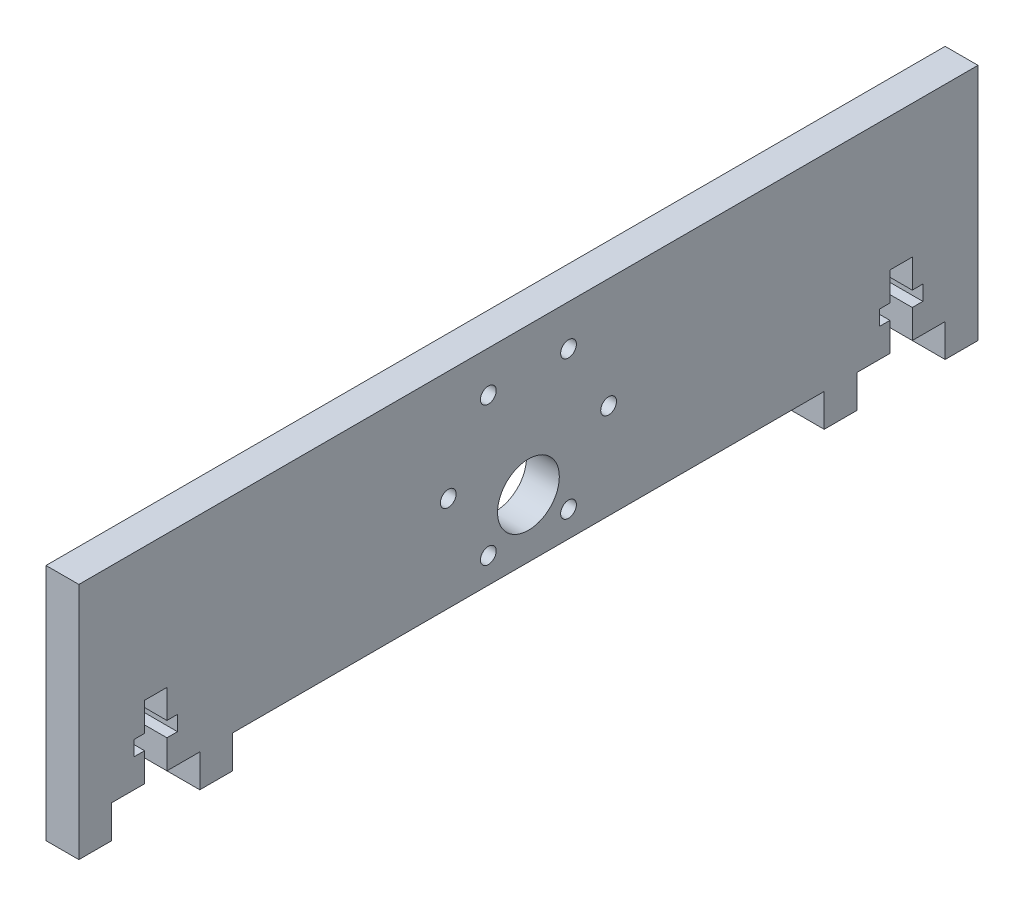
SolidWorks part; units mm, degrees
ref_plane "Front Plane" through (0, 0, 0) normal (0, 0, 1) x (1, 0, 0)
ref_plane "Top Plane" through (0, 0, 0) normal (0, 1, 0) x (1, 0, 0)
ref_plane "Right Plane" through (0, 0, 0) normal (1, 0, 0) x (0, 0, -1)
sketch "Motor plate" plane through (0, 0, 0) normal (1, 0, 0) x (0, 0, -1)
  line L0 (0, -1.4386) -> (7.747, 11.9796) construction
  line L1 (57.15, -19.8536) -> (-57.15, -19.8536)
  line L2 (57.15, -19.8536) -> (57.15, 19.8536) construction
  line L3 (57.15, 19.8536) -> (-57.15, 19.8536)
  line L4 (-57.15, -19.8536) -> (-57.15, 19.8536) construction
  line L5 (57.15, -19.8536) -> (-57.15, 19.8536) construction
  line L6 (57.15, 19.8536) -> (-57.15, -19.8536) construction
  line L7 (86.868, 19.8536) -> (57.15, 19.8536)
  line L8 (86.868, -19.8536) -> (86.868, 19.8536)
  line L9 (-86.868, -26.2036) -> (86.868, -26.2036) construction
  line L13 (0, 19.8536) -> (0, -19.8536) construction
  line L21 (-86.868, -19.8536) -> (-86.868, 19.8536)
  line L22 (-86.868, 19.8536) -> (-57.15, 19.8536)
  circle A0 centre (7.747, 11.9796) radius 1.524
  circle A1 centre (15.494, -1.4386) radius 1.524
  circle A2 centre (7.747, -14.8568) radius 1.524
  circle A3 centre (-7.747, -14.8568) radius 1.524
  circle A4 centre (-15.494, -1.4386) radius 1.524
  circle A5 centre (-7.747, 11.9796) radius 1.524
  circle A6 centre (0, -8.5506) radius 5.969
  circle A7 centre (0, -1.4386) radius 18.415 construction
  point P0 (0, 0)
  point P15 (0, -1.4386)
  point P32 (0, -1.4386)
  line B0 (-80.518, -19.8536) -> (-80.518, -26.2036)
  line B1 (-80.518, -26.2036) -> (-86.868, -26.2036)
  line B2 (-86.868, -26.2036) -> (-86.868, -19.8536)
  line B3 (-74.168, -19.8536) -> (-74.168, -14.3186)
  line B4 (-74.168, -14.3186) -> (-76.209, -14.3186)
  line B5 (-76.209, -14.3186) -> (-76.209, -11.4186)
  line B6 (-76.209, -11.4186) -> (-74.168, -11.4186)
  line B7 (-74.168, -11.4186) -> (-74.168, -5.8836)
  line B8 (-74.168, -5.8836) -> (-69.85, -5.8836)
  line B9 (-69.85, -5.8836) -> (-69.85, -11.4186)
  line B10 (-69.85, -11.4186) -> (-67.809, -11.4186)
  line B11 (-67.809, -11.4186) -> (-67.809, -14.3186)
  line B12 (-67.809, -14.3186) -> (-69.85, -14.3186)
  line B13 (-69.85, -14.3186) -> (-69.85, -19.8536)
  line B14 (-72.009, -5.8836) -> (-72.009, -19.8536) construction
  line B15 (-63.5, -19.8536) -> (-69.85, -19.8536)
  line B16 (-57.15, -26.2036) -> (-57.15, -19.8536)
  line B17 (-80.518, -19.8536) -> (-74.168, -19.8536)
  line B18 (-63.5, -26.2036) -> (-57.15, -26.2036)
  line B19 (-63.5, -19.8536) -> (-63.5, -26.2036)
  line B20 (80.518, -19.8536) -> (80.518, -26.2036)
  line B21 (80.518, -26.2036) -> (86.868, -26.2036)
  line B22 (86.868, -26.2036) -> (86.868, -19.8536)
  line B23 (74.168, -19.8536) -> (74.168, -14.3186)
  line B24 (74.168, -14.3186) -> (76.209, -14.3186)
  line B25 (76.209, -14.3186) -> (76.209, -11.4186)
  line B26 (76.209, -11.4186) -> (74.168, -11.4186)
  line B27 (74.168, -11.4186) -> (74.168, -5.8836)
  line B28 (74.168, -5.8836) -> (69.85, -5.8836)
  line B29 (69.85, -5.8836) -> (69.85, -11.4186)
  line B30 (69.85, -11.4186) -> (67.809, -11.4186)
  line B31 (67.809, -11.4186) -> (67.809, -14.3186)
  line B32 (67.809, -14.3186) -> (69.85, -14.3186)
  line B33 (69.85, -14.3186) -> (69.85, -19.8536)
  line B34 (72.009, -5.8836) -> (72.009, -19.8536) construction
  line B35 (63.5, -19.8536) -> (69.85, -19.8536)
  line B36 (57.15, -26.2036) -> (57.15, -19.8536)
  line B37 (80.518, -19.8536) -> (74.168, -19.8536)
  line B38 (63.5, -26.2036) -> (57.15, -26.2036)
  line B39 (63.5, -19.8536) -> (63.5, -26.2036)
  dimension "D3" = 30
  dimension "D4" = 15.494
  dimension "D5" = 3.048
  dimension "D8" = 11.938
  dimension "D2" = 36.83
  dimension "D1" = 114.3
  dimension "D6" = 6.35
  dimension "D7" = 6
  dimension "D9" = 7.112
sketch_block_instance "Male T-slot assembly-3"
sketch_block "Male T-slot assembly" parameters "D1"=6.35, "D2"=6.35, "D3"=4.318, "D4"=2.9, "D5"=8.4, "D6"=13.97, "D7"=6.35
sketch_block_instance "Male T-slot assembly-5"
extrude "Boss-Extrude1" add sketch "Motor plate" along normal blind 6.35 contours B39 B35 B33 B32 B31 B30 B29 B28 B27 B26 B25 B24 B23 B37 B20 B21 B22 L8 L7 L3 L22 L21 B2 B1 B0 B17 B3 B4 B5 B6 B7 B8 B9 B10 B11 B12 B13 B15 B19 B18 B16 L1 B36 B38 region at (0, -0.1238, 0)
equation "\"D1@Motor plate\"=\"Wheel Diameter\" + 2 * \"Sheet Thickness\""
equation "\"Ball Diameter\"= 1.75in"
equation "\"Sheet Thickness\"= 0.25in"
equation "\"Screw Diameter\"= .17in"
equation "\"Robot Diameter\"= 14in"
equation "\"Castor Screw Diameter\"= 0.22in"
equation "\"Wheel Diameter\" = 4in"
equation "\"Nut Diameter\" = 8.4mm"
equation "\"Nut Height\" = 2.9mm"
equation "\"Screw Height\" = 0.55in"
equation "\"D1@Boss-Extrude1\"=\"Sheet Thickness\""
equation "\"D3@Motor plate\"=360/12deg"
equation "\"Ball Radius\" = \"Ball Diameter\"/2"
equation "\"Pulley Diameter\" = 1in"
equation "\"Reactor Height\" = 14in"
equation "\"Elevator Height\" = 11.5in"
equation "\"Elevator Width\" = \"Ball Diameter\" + 0.25in"
equation "\"Elevator Bearing Diameter\" = sqr(2*(\"Sheet Thickness\"^2)) + 0.2in"
equation "\"Elevator Axle Endcap Diameter\" = \"Pulley Diameter\" + 0.25in"
equation "\"Elevator Axle Length\" = \"Elevator Width\" + 8*\"Sheet Thickness\""
equation "\"Elevator Clearance from Axis\" = 3.5in"
equation "\"Elevator Horizontal Clearance\" = \"Elevator Width\" + 0.5in"
equation "\"Claw Horizontal Seperation\" = (\"Elevator Width\"/2) - (1.5 * \"Sheet Thickness\") - 0.15in"
equation "\"Claw Radius\" = \"Ball Radius\" + 0.1in"
equation "\"Castor Wheel Height\" = 1.25in"
